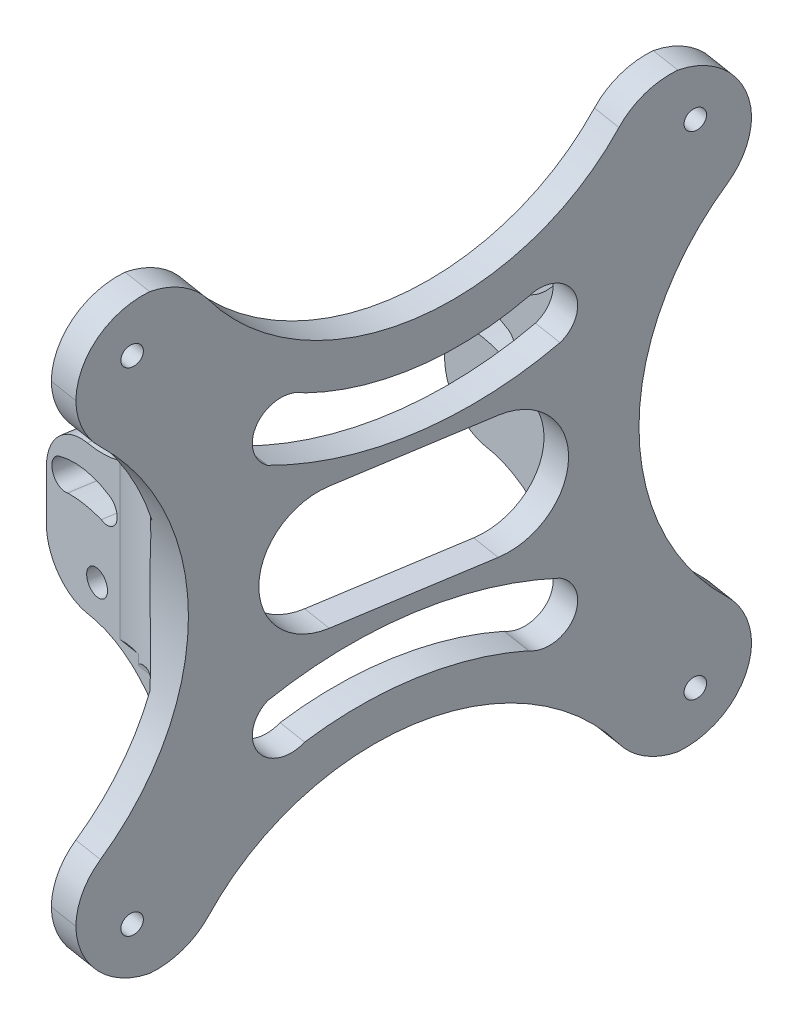
SolidWorks part; units mm, degrees
ref_plane "Plan de face" through (0, 0, 0) normal (0, 0, 1) x (1, 0, 0)
ref_plane "Plan de dessus" through (0, 0, 0) normal (0, 1, 0) x (1, 0, 0)
ref_plane "Plan de droite" through (0, 0, 0) normal (1, 0, 0) x (0, 0, -1)
sketch "Esquisse2" plane through (0.9062, 0, -5.7217) normal (-0.1564, 0, 0.9877) x (0.9877, 0, 0.1564)
  line L2 (19, 13.8449) -> (50, 13.8449)
  line L3 (19, 13.8449) -> (19, -16.1551)
  line L4 (19, -16.1551) -> (50, -16.1551)
  line L5 (50, 13.8449) -> (50, -16.1551)
  circle A0 centre (31.3973, -9.3696) radius 2.55
  arc A9 (34.496, 7.5776) -> (32.4193, 2.2798) centre (33.4577, 4.9287) cw
  arc A11 (22.1493, 7.5776) -> (24.2261, 2.2798) centre (23.1877, 4.9287) ccw
  arc A12 (22.1493, 7.5776) -> (34.496, 7.5776) centre (28.3227, -8.1708) cw
  arc A14 (24.2261, 2.2798) -> (32.4193, 2.2798) centre (28.3227, -21.4961) cw
  dimension "D1" = 31
extrude "Boss.-Extru.1" add sketch "Esquisse2" along normal blind 6
sketch "Esquisse8" plane through (11.0275, 0, -69.6251) normal (0.1564, 0, -0.9877) x (-0.9877, 0, -0.1564)
  line L1 (-50, 13.8449) -> (-19, 13.8449)
  line L2 (-50, 13.8449) -> (-50, -16.1551)
  line L3 (-50, -16.1551) -> (-19, -16.1551)
  line L4 (-19, 13.8449) -> (-19, -16.1551)
  circle A0 centre (-28.3236, -8.142) radius 2.55
  arc A1 (-22.1493, 7.5776) -> (-24.2261, 2.2798) centre (-23.1877, 4.9287) cw
  arc A2 (-34.496, 7.5776) -> (-32.4193, 2.2798) centre (-33.4577, 4.9287) ccw
  arc A3 (-34.496, 7.5776) -> (-22.1493, 7.5776) centre (-28.3227, -8.1708) cw
  arc A5 (-32.4193, 2.2798) -> (-24.2261, 2.2798) centre (-28.3227, -20.7951) cw
extrude "Boss.-Extru.3" add sketch "Esquisse8" along normal blind 6 separate body
sketch "Esquisse7" plane through (49.3844, 0, 7.8217) normal (0.9877, 0, 0.1564) x (0.1564, 0, -0.9877)
  line L6 (-21.8658, 59.4655) -> (98.1342, 59.4655)
  line L7 (-21.8658, 59.4655) -> (-21.8658, -60.5345)
  line L8 (-21.8658, -60.5345) -> (98.1342, -60.5345)
  line L9 (98.1342, 59.4655) -> (98.1342, -60.5345)
  circle A0 centre (-11.8658, 49.4655) radius 2
  circle A1 centre (88.1342, 49.4655) radius 2
  circle A2 centre (88.1342, -50.5345) radius 2
  circle A3 centre (-11.8658, -50.5345) radius 2
  dimension "D5" = 4
  dimension "D9" = 4
  dimension "D11" = 4
  dimension "D12" = 4
  dimension "D1" = 100
  dimension "D2" = 100
  dimension "D3" = 120
  dimension "D4" = 120
  dimension "D14" = 100
  dimension "D15" = 100
extrude "Boss.-Extru.5" add sketch "Esquisse7" along normal blind 6
sketch "Esquisse13" plane through (49.3844, 0, 7.8217) normal (-0.9877, 0, -0.1564) x (-0.1564, 0, 0.9877)
  line L0 (-98.1342, -60.5345) -> (-98.1342, 59.4655) construction
  line L1 (-76.493, 13.8449) -> (-98.1342, 13.8449)
  line L2 (-76.493, 13.8449) -> (-76.493, -16.1551)
  line L3 (-76.493, -16.1551) -> (-98.1342, -16.1551)
  line L4 (-98.1342, 13.8449) -> (-98.1342, -16.1551)
  line L5 (21.8658, 59.4655) -> (21.8658, -60.5345) construction
  line L6 (0.207, 13.8449) -> (21.8658, 13.8449)
  line L7 (0.207, 13.8449) -> (0.207, -16.1551)
  line L8 (0.207, -16.1551) -> (21.8658, -16.1551)
  line L9 (21.8658, 13.8449) -> (21.8658, -16.1551)
extrude "Boss.-Extru.6" add sketch "Esquisse13" along normal blind 13
sketch "Esquisse9" plane through (49.3844, 0, 7.8217) normal (-0.9877, 0, -0.1564) x (-0.1564, 0, 0.9877)
  line L0 (-98.1342, -60.5345) -> (-98.1342, -16.1551) construction
  line L1 (-98.1342, 59.4655) -> (21.8658, 59.4655) construction
  line L2 (21.8658, -60.5345) -> (-98.1342, -60.5345) construction
  line L4 (21.8658, 59.4655) -> (21.8658, 13.8449) construction
  line L5 (-98.1342, 39.4655) -> (-98.1342, -40.5345)
  line L6 (-78.1342, -60.5345) -> (1.8658, -60.5345)
  line L7 (21.8658, 39.4655) -> (21.8658, -40.5345)
  line L8 (1.8658, 59.4655) -> (-78.1342, 59.4655)
  arc A0 (-98.1342, 39.4655) -> (-98.1342, -40.5345) centre (-128.1342, -0.5345) cw
  arc A1 (-78.1342, 59.4655) -> (1.8658, 59.4655) centre (-38.1342, 80.081) ccw
  arc A2 (21.8658, 39.4655) -> (21.8658, -40.5345) centre (51.8658, -0.5345) ccw
  arc A3 (1.8658, -60.5345) -> (-78.1342, -60.5345) centre (-38.1342, -81.15) ccw
  dimension "D3" = 50
  dimension "D6" = 45
  dimension "D9" = 50
  dimension "D12" = 45
  dimension "D1" = 20
  dimension "D2" = 20
  dimension "D4" = 20
  dimension "D5" = 20
  dimension "D7" = 20
  dimension "D8" = 20
  dimension "D10" = 20
  dimension "D11" = 20
extrude "Enlèv. mat.-Extru.1" cut sketch "Esquisse9" against normal blind 10 and the other way blind 13
sketch "Esquisse10" plane through (49.3844, 0, 7.8217) normal (-0.9877, 0, -0.1564) x (-0.1564, 0, 0.9877)
  line L0 (-53.1342, -0.5345) -> (-23.1342, -0.5345) construction
  line L1 (-53.1342, 11.9655) -> (-23.1342, 11.9655)
  line L2 (-53.1342, -13.0345) -> (-23.1342, -13.0345)
  line L3 (-98.1342, 59.4655) -> (-78.1342, 59.4655) construction
  line L5 (-98.1342, 39.4655) -> (-98.1342, 59.4655) construction
  line L6 (21.8658, 59.4655) -> (21.8658, 39.4655) construction
  arc A0 (-53.1342, 11.9655) -> (-53.1342, -13.0345) centre (-53.1342, -0.5345) ccw
  arc A1 (-23.1342, -13.0345) -> (-23.1342, 11.9655) centre (-23.1342, -0.5345) ccw
  point P2 (-38.1342, -0.5345)
  dimension "D4" = 12.5
  dimension "D1" = 60
  dimension "D2" = 45
  dimension "D3" = 45
extrude "Enlèv. mat.-Extru.2" cut sketch "Esquisse10" against normal blind 10
fillet "Congé1" radius 14 12 edges at (64.5704, 59.4655, -68.8812) (67.6991, 59.4655, -88.635) (67.6991, -40.5345, -88.635) (52.0556, 59.4655, 10.1339) (48.9269, 59.4655, 29.8876) (48.9269, -40.5345, 29.8876) (67.6991, -60.5345, -88.635) (52.0556, -60.5345, 10.1339) (48.9269, 39.4655, 29.8876) (67.6991, 39.4655, -88.635) (64.5704, -60.5345, -68.8812) (48.9269, -60.5345, 29.8876)
fillet "Congé2" radius 10 4 edges at (30.2629, 13.8449, -69.6159) (19.203, 13.8449, 0.2136) (30.2629, -16.1551, -69.6159) (19.203, -16.1551, 0.2136)
sketch "Esquisse16" plane through (49.3844, 0, 7.8217) normal (-0.9877, 0, -0.1564) x (-0.1564, 0, 0.9877)
  line L1 (-70.493, -16.1551) -> (-76.493, -16.1551)
  line L2 (-70.493, -16.1551) -> (-70.493, -36.1551)
  line L3 (-70.493, -36.1551) -> (-76.493, -36.1551)
  line L4 (-76.493, -16.1551) -> (-76.493, -36.1551)
  line L5 (-70.493, 13.8449) -> (-76.493, 13.8449)
  line L6 (-70.493, 13.8449) -> (-70.493, 33.8449)
  line L7 (-70.493, 33.8449) -> (-76.493, 33.8449)
  line L8 (-76.493, 13.8449) -> (-76.493, 33.8449)
  line L9 (-5.793, 13.8449) -> (0.207, 13.8449)
  line L10 (-5.793, 13.8449) -> (-5.793, 33.8449)
  line L11 (-5.793, 33.8449) -> (0.207, 33.8449)
  line L12 (0.207, 13.8449) -> (0.207, 33.8449)
  line L13 (-5.793, -16.1551) -> (0.207, -16.1551)
  line L14 (-5.793, -16.1551) -> (-5.793, -36.1551)
  line L15 (-5.793, -36.1551) -> (0.207, -36.1551)
  line L16 (0.207, -16.1551) -> (0.207, -36.1551)
  dimension "D1" = 20
  dimension "D2" = 20
  dimension "D3" = 20
  dimension "D4" = 20
  dimension "D5" = 6
  dimension "D6" = 6
  dimension "D7" = 6
  dimension "D8" = 6
extrude "Boss.-Extru.7" add sketch "Esquisse16" along normal blind 21
sketch "Esquisse17" plane through (-0.0324, 0, 0.2045) normal (-0.1564, 0, 0.9877) x (0.9877, 0, 0.1564)
  line L0 (50, 33.8449) -> (29, 33.8449)
  line L1 (29, 33.8449) -> (29, 13.8449)
  line L2 (29, -16.1551) -> (29, -36.1551)
  line L3 (29, -36.1551) -> (50, -36.1551)
  arc A0 (29, -16.1551) -> (50, -36.1551) centre (29.5, -36.6551) cw
  arc A1 (29, 13.8449) -> (50, 33.8449) centre (29.5, 34.3449) ccw
extrude "Enlèv. mat.-Extru.5" cut sketch "Esquisse17" against normal blind 102
sketch "Esquisse11" plane through (49.3844, 0, 7.8217) normal (-0.9877, 0, -0.1564) x (-0.1564, 0, 0.9877)
  circle A0 centre (-88.1342, 49.4655) radius 3.6
  circle A1 centre (11.8658, 49.4655) radius 3.6
  circle A2 centre (11.8658, -50.5345) radius 3.6
  circle A3 centre (-88.1342, -50.5345) radius 3.6
  dimension "D1" = 7.2
  dimension "D2" = 7.2
  dimension "D3" = 7.2
  dimension "D4" = 7.2
extrude "Enlèv. mat.-Extru.3" cut sketch "Esquisse11" against normal blind 2
sketch "Esquisse14" plane through (0, -16.1551, 0) normal (0, -1, 0) x (1, 0, 0)
  line L0 (36.5121, 5.9925) -> (35.8611, 10.1027)
  line L1 (35.8611, 10.1027) -> (48.701, 12.1364)
  line L2 (48.5106, -69.7632) -> (49.1589, -73.856)
  line L3 (49.1589, -73.856) -> (61.9988, -71.8224)
  arc A0 (48.5106, -69.7632) -> (61.9988, -71.8224) centre (53.1542, -84.5512) cw
  arc A1 (36.5121, 5.9925) -> (48.701, 12.1364) centre (36.3426, 21.4916) ccw
extrude "Enlèv. mat.-Extru.4" cut sketch "Esquisse14" against normal blind 50
fillet "Congé3" radius 2 4 edges at (57.1757, 13.8449, -68.3908) (45.1615, 13.8449, 7.3625) (45.1615, -16.1551, 7.3625) (57.1757, -16.1551, -68.3908)
sketch "Esquisse18" plane through (49.3844, 0, 7.8217) normal (-0.9877, 0, -0.1564) x (-0.1564, 0, 0.9877)
  arc A4 (-58.5309, 30.6356) -> (-18.758, 30.1817) centre (-38.0971, 78.369) ccw
  arc A5 (-64.1065, 20.1757) -> (-12.1795, 20.1757) centre (-38.143, 81.8699) ccw
  arc A6 (-58.5309, -31.7046) -> (-18.758, -31.2507) centre (-37.9749, -90.1471) cw
  arc A7 (-64.1065, -21.2447) -> (-12.1795, -21.2447) centre (-38.143, -90.1935) cw
  arc A8 (-58.5309, 30.6356) -> (-64.1065, 20.1757) centre (-61.3187, 25.4057) ccw
  arc A9 (-18.758, 30.1817) -> (-12.1795, 20.1757) centre (-15.4687, 25.1787) cw
  arc A10 (-64.1065, -21.2447) -> (-58.5309, -31.7046) centre (-61.3187, -26.4746) ccw
  arc A11 (-12.1795, -21.2447) -> (-18.758, -31.2507) centre (-15.4687, -26.2477) cw
extrude "Enlèv. mat.-Extru.6" cut sketch "Esquisse18" against normal blind 10
